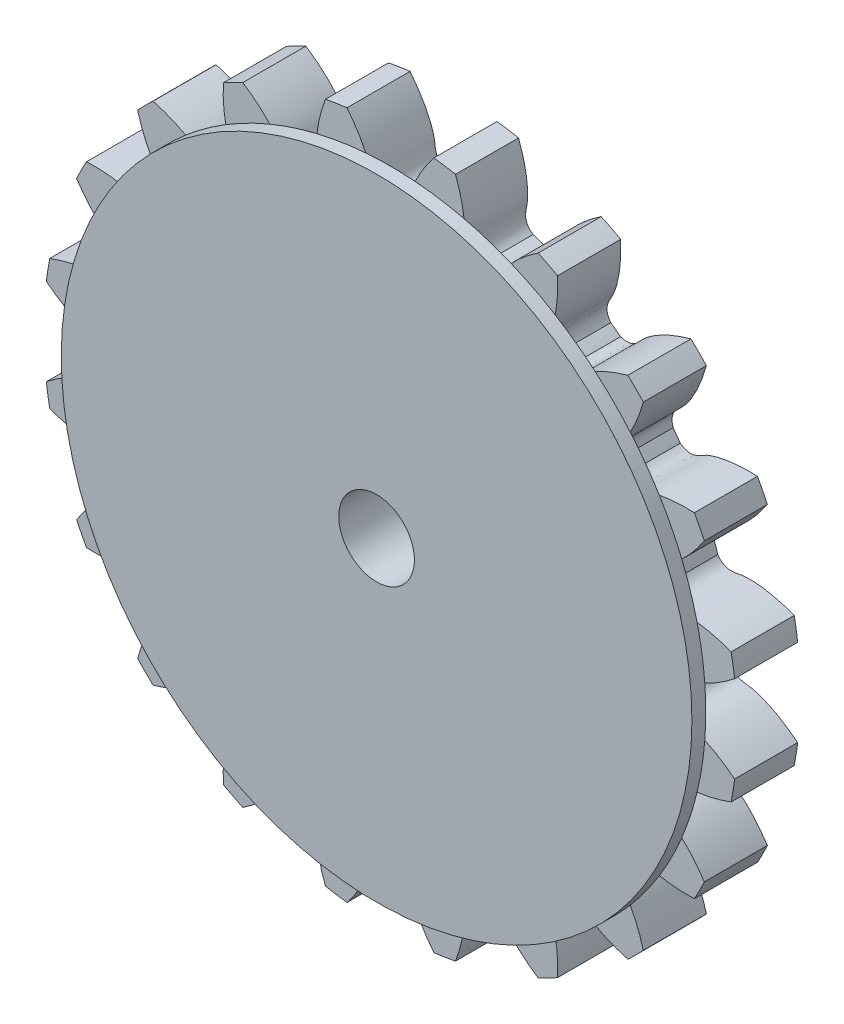
SolidWorks part; units mm, degrees
material "尼龙 6/10"
ref_plane "前视基准面" through (0, 0, 0) normal (0, 0, 1) x (1, 0, 0)
ref_plane "上视基准面" through (0, 0, 0) normal (0, 1, 0) x (1, 0, 0)
ref_plane "右视基准面" through (0, 0, 0) normal (1, 0, 0) x (0, 0, -1)
sketch "草图1" plane through (0, 0, 0) normal (0, 0, 1) x (1, 0, 0)
  circle A0 centre (0, 0) radius 5.5
extrude "凸台-拉伸1" add sketch "草图1" along normal blind 1
ref_axis "基准轴1" through (0, 0, -1.5) along (0, 0, 1)
sketch "草图2" plane through (0, 0, 0) normal (0, 0, 1) x (1, 0, 0)
  line L0 (0, 0) -> (0, 5.5) construction
  circle A0 centre (0, 0) radius 5.5 construction
  arc A1 (0.0967, 4.3739) -> (-0.0967, 4.3739) centre (0, 0) ccw
  arc A2 (1.5906, 6.2491) -> (-1.5906, 6.2491) centre (0, 0) ccw
  spline S0 degree 3 poles (0.0967, 4.3739) (0.3056, 4.4467) (0.2785, 4.5936) (0.3064, 4.735) (0.3094, 4.7488) (0.3132, 4.7643) (0.3176, 4.7816) (0.323, 4.8006) (0.3293, 4.8213) (0.3365, 4.8436) (0.3448, 4.8676) (0.3543, 4.8932) (0.3649, 4.9203) (0.3768, 4.9489) (0.3901, 4.979) (0.4047, 5.0106) (0.4208, 5.0435) (0.4383, 5.0778) (0.4575, 5.1134) (0.4783, 5.1502) (0.5008, 5.1882) (0.525, 5.2274) (0.551, 5.2676) (0.5789, 5.3089) (0.6087, 5.3511) (0.6404, 5.3943) (0.6741, 5.4383) (0.7099, 5.4831) (0.7477, 5.5286) (0.7877, 5.5748) (0.8299, 5.6215) (0.8743, 5.6688) (0.9209, 5.7165) (0.9698, 5.7646) (1.0211, 5.813) (1.0747, 5.8617) (1.1306, 5.9104) (1.189, 5.9593) (1.2498, 6.0082) (1.313, 6.057) (1.3788, 6.1056) (1.4707, 6.1708) (1.542, 6.2182) (1.5906, 6.2491) knots 0 0 0 0 0.165916 0.170906 0.176664 0.183189 0.190482 0.198542 0.207371 0.216967 0.22733 0.238462 0.250361 0.263027 0.276462 0.290664 0.305634 0.321371 0.337876 0.355149 0.37319 0.391998 0.411574 0.431917 0.453028 0.474907 0.497554 0.520968 0.54515 0.570099 0.595817 0.622302 0.649554 0.677575 0.706363 0.735918 0.766242 0.797333 0.829191 0.861818 0.895212 0.929373 1 1 1 1
  spline S1 degree 3 poles (-0.0967, 4.3739) (-0.3056, 4.4467) (-0.2785, 4.5936) (-0.3064, 4.735) (-0.3094, 4.7488) (-0.3132, 4.7643) (-0.3176, 4.7816) (-0.323, 4.8006) (-0.3293, 4.8213) (-0.3365, 4.8436) (-0.3448, 4.8676) (-0.3543, 4.8932) (-0.3649, 4.9203) (-0.3768, 4.9489) (-0.3901, 4.979) (-0.4047, 5.0106) (-0.4208, 5.0435) (-0.4383, 5.0778) (-0.4575, 5.1134) (-0.4783, 5.1502) (-0.5008, 5.1882) (-0.525, 5.2274) (-0.551, 5.2676) (-0.5789, 5.3089) (-0.6087, 5.3511) (-0.6404, 5.3943) (-0.6741, 5.4383) (-0.7099, 5.4831) (-0.7477, 5.5286) (-0.7877, 5.5748) (-0.8299, 5.6215) (-0.8743, 5.6688) (-0.9209, 5.7165) (-0.9698, 5.7646) (-1.0211, 5.813) (-1.0747, 5.8617) (-1.1306, 5.9104) (-1.189, 5.9593) (-1.2498, 6.0082) (-1.313, 6.057) (-1.3788, 6.1056) (-1.4707, 6.1708) (-1.542, 6.2182) (-1.5906, 6.2491) knots 0 0 0 0 0.165916 0.170906 0.176664 0.183189 0.190482 0.198542 0.207371 0.216967 0.22733 0.238462 0.250361 0.263027 0.276462 0.290664 0.305634 0.321371 0.337876 0.355149 0.37319 0.391998 0.411574 0.431917 0.453028 0.474907 0.497554 0.520968 0.54515 0.570099 0.595817 0.622302 0.649554 0.677575 0.706363 0.735918 0.766242 0.797333 0.829191 0.861818 0.895212 0.929373 1 1 1 1
extrude "切除-拉伸1" cut sketch "草图2" along normal through all
pattern_circular "阵列(圆周)1" count 20 every 18 about axis through (0, 0, -1.5) along (0, 0, 1) of "切除-拉伸1"
sketch "草图3" [suppressed] plane through (0, 0, 0) normal (0, 0, 1) x (1, 0, 0)
  circle A0 centre (0, 0) radius 5 construction
  dimension "Dn" = 10
sketch "草图4" plane through (0, 0, 1) normal (0, 0, 1) x (1, 0, 0)
  circle A0 centre (0, 0) radius 5
  dimension "D1" = 10
extrude "凸台-拉伸2" add sketch "草图4" along normal blind 0.22
sketch "草图5" plane through (0, 0, 1.22) normal (0, 0, 1) x (1, 0, 0)
  circle A0 centre (0, 0) radius 0.6
  dimension "D1" = 1.2
extrude "切除-拉伸2" cut sketch "草图5" against normal through all
